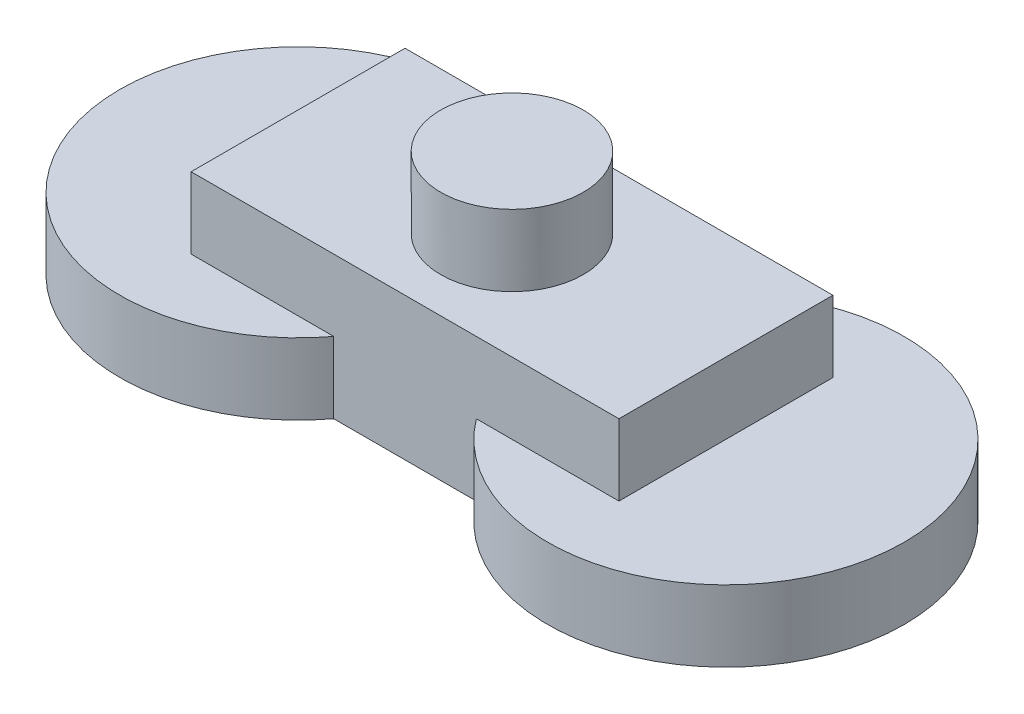
SolidWorks part; units mm, degrees
ref_plane "정면" through (0, 0, 0) normal (0, 0, 1) x (1, 0, 0)
ref_plane "윗면" through (0, 0, 0) normal (0, 1, 0) x (1, 0, 0)
ref_plane "우측면" through (0, 0, 0) normal (1, 0, 0) x (0, 0, -1)
sketch "스케치1" plane through (0, 0, 0) normal (0, 1, 0) x (1, 0, 0)
  line L1 (20.6892, -38.6286) -> (-39.3108, -38.6286)
  line L2 (20.6892, -38.6286) -> (20.6892, -8.6286)
  line L3 (20.6892, -8.6286) -> (-39.3108, -8.6286)
  line L4 (-39.3108, -38.6286) -> (-39.3108, -8.6286)
  circle A0 centre (-39.3108, -23.6286) radius 25
  circle A1 centre (20.6892, -23.6286) radius 25
  circle A2 centre (-9.3108, -23.6286) radius 10
extrude "보스-돌출1" add sketch "스케치1" along normal blind 10 contours L1 A1 L3 L2 | L3 A0 L1 L4 region at (27.23, 0, 23.6286) region at (-45.8516, 0, 23.6286)
extrude "보스-돌출2" add sketch "스케치1<3>" along normal blind 20 contours A2 A1 L1 L2 L3 | A2 A1 L3 A0 | A2 A0 L1 A1 | A2 A0 L3 L4 L1 region at (9.8512, 0, 23.6286) region at (-9.3108, 0, 35.9079) region at (-28.4727, 0, 23.6286) region at (-9.3108, 0, 11.3493)
sketch "스케치1<3>" plane through (0, 0, 0) normal (0, 1, 0) x (1, 0, 0) same geometry as "스케치1"
sketch "스케치3" plane through (0, 20, 0) normal (0, 1, 0) x (1, 0, 0)
sketch "스케치6" plane through (0, 10, 0) normal (0, 1, 0) x (1, 0, 0)
  circle A1 centre (-9.3108, -23.6286) radius 10
sketch "스케치7" plane through (0, 0, 0) normal (0, -1, 0) x (1, 0, 0)
  circle A0 centre (-9.3108, 23.6286) radius 10
extrude "보스-돌출4" add sketch "스케치7" against normal blind 30
